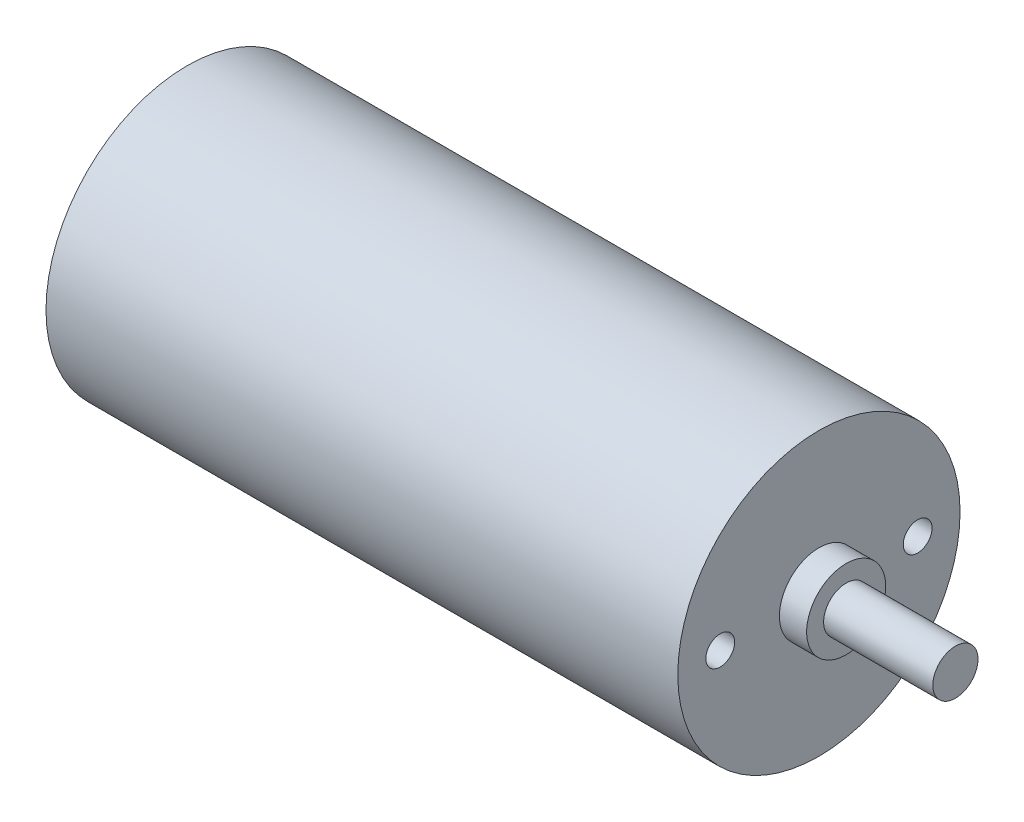
SolidWorks part; units mm, degrees
ref_plane "Front Plane" through (0, 0, 0) normal (0, 0, 1) x (1, 0, 0)
ref_plane "Top Plane" through (0, 0, 0) normal (0, 1, 0) x (1, 0, 0)
ref_plane "Right Plane" through (0, 0, 0) normal (1, 0, 0) x (0, 0, -1)
sketch "Sketch1" plane through (0, 0, 0) normal (1, 0, 0) x (0, 0, -1)
  line L0 (-12.44, 0) -> (-8.7, 0) construction
  line L1 (0, 12.44) -> (0, -12.44) construction
  circle A0 centre (0, 0) radius 12.44
  circle A1 centre (0, 0) radius 3.485
  circle A2 centre (0, 0) radius 1.99
  circle A3 centre (-8.7, 0) radius 1.27
  circle A4 centre (8.7, 0) radius 1.27
extrude "Boss-Extrude1" add sketch "Sketch1" along normal blind 12.03 contours A2 region at (0, 0, 0)
extrude "Boss-Extrude2" add sketch "Sketch1<3>" along normal blind 2.4 contours A1 A2 region at (0, 0, 3.3864)
sketch "Sketch1<3>" plane through (0, 0, 0) normal (1, 0, 0) x (0, 0, -1) same geometry as "Sketch1"
extrude "Boss-Extrude3" add sketch "Sketch1<4>" against normal blind 55.69 separate body contours A0 A1 A3 A4 region at (0, 0, 12.0881)
sketch "Sketch1<4>" plane through (0, 0, 0) normal (1, 0, 0) x (0, 0, -1) same geometry as "Sketch1"
